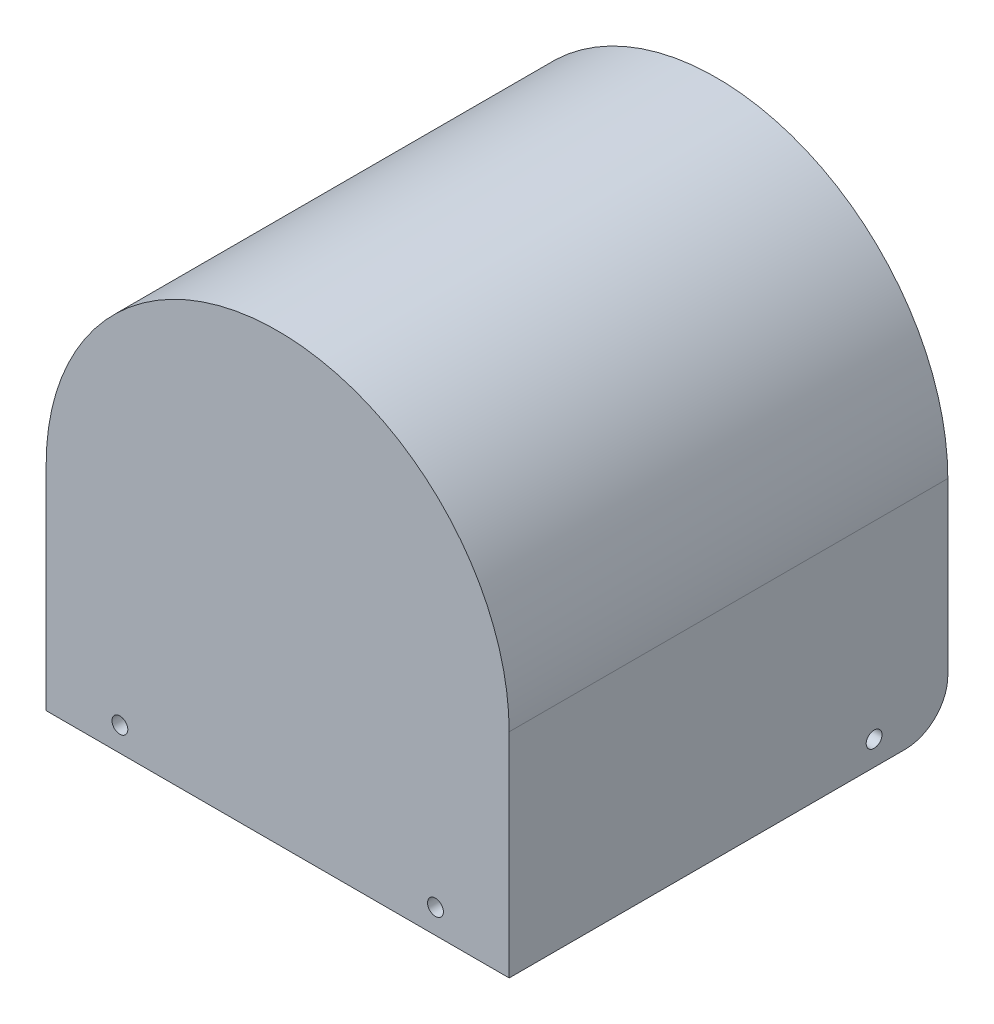
SolidWorks part; units mm, degrees
ref_plane "Front Plane" through (0, 0, 0) normal (0, 0, 1) x (1, 0, 0)
ref_plane "Top Plane" through (0, 0, 0) normal (0, 1, 0) x (1, 0, 0)
ref_plane "Right Plane" through (0, 0, 0) normal (1, 0, 0) x (0, 0, -1)
sketch "Sketch1" plane through (0, 0, 0) normal (0, 0, 1) x (1, 0, 0)
  line L0 (-36, 0) -> (-36, -35)
  line L1 (36, 0) -> (36, -35)
  line L2 (38, 0) -> (38, -35)
  line L3 (-38, 0) -> (-38, -35)
  line L4 (-38, -35) -> (-36, -35)
  line L5 (36, -35) -> (38, -35)
  arc A0 (-36, 0) -> (36, 0) centre (0, 0) cw
  arc A1 (-38, 0) -> (38, 0) centre (0, 0) cw
  dimension "D1" = 36
  dimension "D2" = 35
  dimension "D3" = 2
extrude "Boss-Extrude1" add sketch "Sketch1" along normal blind 72
sketch "Sketch2" plane through (0, 0, 0) normal (0, 1, 0) x (1, 0, 0)
  line L0 (-36, -72) -> (36, -72) construction
  line L1 (-36, -72) -> (36, -72)
  line L2 (-36, -72) -> (-36, -70)
  line L3 (-36, -70) -> (36, -70)
  line L4 (36, -72) -> (36, 0) construction
  line L5 (36, -70) -> (36, -72)
  dimension "D1" = 2
extrude "Boss-Extrude2" add sketch "Sketch2" against normal up to surface (35 mm away) and the other way up to surface up to face at (37, -35, 36) other way up to face at (0, 18, 36)
sketch "Sketch3" plane through (0, 0, 72) normal (0, 0, 1) x (1, 0, 0)
  line L0 (-38, -31) -> (38, -31) construction
  line L1 (-38, 0) -> (-38, -35) construction
  line L2 (38, -35) -> (38, 0) construction
  line L3 (-38, -35) -> (38, -35) construction
  line L4 (0, -31) -> (0, -35) construction
  circle A0 centre (-25.9, -31) radius 1.3
  circle A1 centre (25.9, -31) radius 1.3
  dimension "D3" = 2.6
  dimension "D1" = 4
  dimension "D2" = 51.8
extrude "Cut-Extrude1" cut sketch "Sketch3" against normal blind 10
sketch "Sketch4" plane through (38, 0, 0) normal (1, 0, 0) x (0, 0, -1)
  line L0 (-12.1, -35) -> (-12.1, 0) construction
  line L1 (-72, -35) -> (0, -35) construction
  line L2 (-72, 0) -> (0, 0) construction
  line L3 (0, -35) -> (0, 0) construction
  circle A0 centre (-12.1, -31) radius 1.3
  dimension "D2" = 2.6
  dimension "D1" = 12.1
  dimension "D3" = 4
extrude "Cut-Extrude2" cut sketch "Sketch4" against normal through all
fillet "Fillet1" radius 7 2 edges at (-37, -35, 0) (37, -35, 0)
